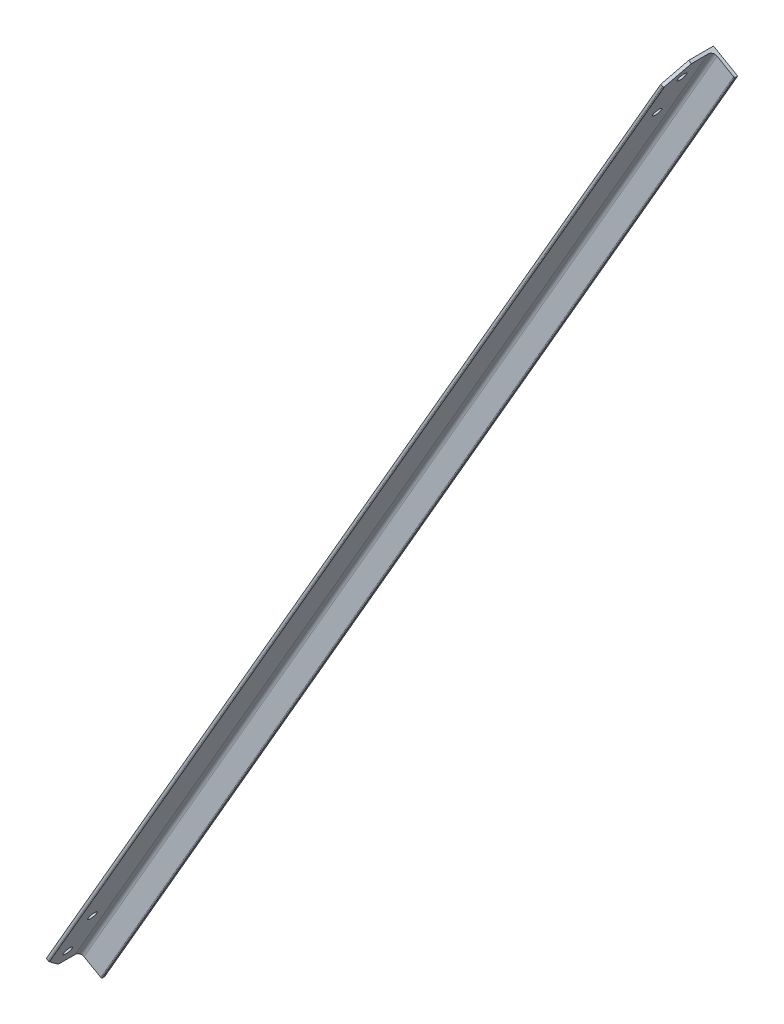
SolidWorks part; units mm, degrees
material "普通碳钢"
ref_plane "前视基准面" through (0, 0, 0) normal (0, 0, 1) x (1, 0, 0)
ref_plane "上视基准面" through (0, 0, 0) normal (0, 1, 0) x (1, 0, 0)
ref_plane "右视基准面" through (0, 0, 0) normal (1, 0, 0) x (0, 0, -1)
sketch "草图1" plane through (0, 0, 0) normal (0, 0, 1) x (1, 0, 0)
  line L0 (0, 0) -> (1020, 1766.6918) construction
  line L1 (0, 0) -> (171.8941, 0) construction
  line L2 (1020, 1766.6918) -> (0, 0)
  dimension "D1" = 60
  dimension "D2" = 2040
other "不等边角钢 70X45X5(1)"
ref_plane "基准面1" through (1020, 1766.6918, 0) normal (-0.5, -0.866, 0) x (0.866, -0.5, 0)
sketch "草图11" plane through (1020, 1766.6918, 0) normal (-0.5, -0.866, 0) x (0.866, -0.5, 0)
  line L0 (0, 70) -> (0, 0)
  line L1 (0, 0) -> (45, 0)
  line L2 (45, 0) -> (45, 3.33)
  line L3 (43.33, 5) -> (12.5, 5)
  line L4 (5, 12.5) -> (5, 68.33)
  line L5 (3.33, 70) -> (0, 70)
  arc A0 (12.5, 5) -> (5, 12.5) centre (12.5, 12.5) cw
  arc A1 (45, 3.33) -> (43.33, 5) centre (43.33, 3.33) ccw
  arc A2 (5, 68.33) -> (3.33, 70) centre (3.33, 68.33) ccw
  point P8 (5, 70)
  point P9 (0, 70)
  point P10 (0, 0)
  point P11 (45, 0)
  point P12 (45, 5)
  point P16 (45, 5)
  point P19 (5, 70)
  point P20 (0, 0)
  dimension "D5" = 7.5
  dimension "D6" = 1.67
  dimension "D1" = 45
  dimension "D2" = 70
  dimension "D3" = 5
  dimension "D4" = 5
sketch "草图12" plane through (0, 0, 0) normal (-0.866, 0.5, 0) x (0, 0, 1)
  line L0 (40, 0) -> (40, 182.7203) construction
  line L1 (70, 0) -> (0, 0) construction
  line L2 (70, 0) -> (70, 2040) construction
  line L3 (118.7853, 30) -> (40, 30) construction
  line L4 (118.7853, 110) -> (40, 110) construction
  circle A0 centre (40, 30) radius 7
  circle A1 centre (40, 110) radius 7
  dimension "D3" = 80
  dimension "D4" = 14
  dimension "D5" = 14
  dimension "D1" = 30
  dimension "D2" = 30
extrude "切除-拉伸1" cut sketch "草图12" against normal up to next
sketch "草图13" plane through (0, 0, 0) normal (-0.866, 0.5, 0) x (0, 0, 1)
  line L1 (40.0047, 2010) -> (40.0047, 1930) construction
  line L2 (70, 0) -> (70, 2040) construction
  line L3 (40.0047, 2010) -> (66.8756, 2010) construction
  line L4 (40.0047, 1930) -> (60.9865, 1930) construction
  line L5 (70, 2040) -> (0, 2040) construction
  circle A0 centre (40.0047, 1930) radius 7
  circle A1 centre (40.0047, 2010) radius 7
  dimension "D1" = 29.9953
  dimension "D2" = 30
  dimension "D3" = 80
extrude "切除-拉伸2" cut sketch "草图13" against normal up to next
chamfer "倒角1" distance 30 1 edges at (1021.4419, 1765.8593, 70)
chamfer "倒角2" distance 30 1 edges at (1.4419, -0.8325, 70)
